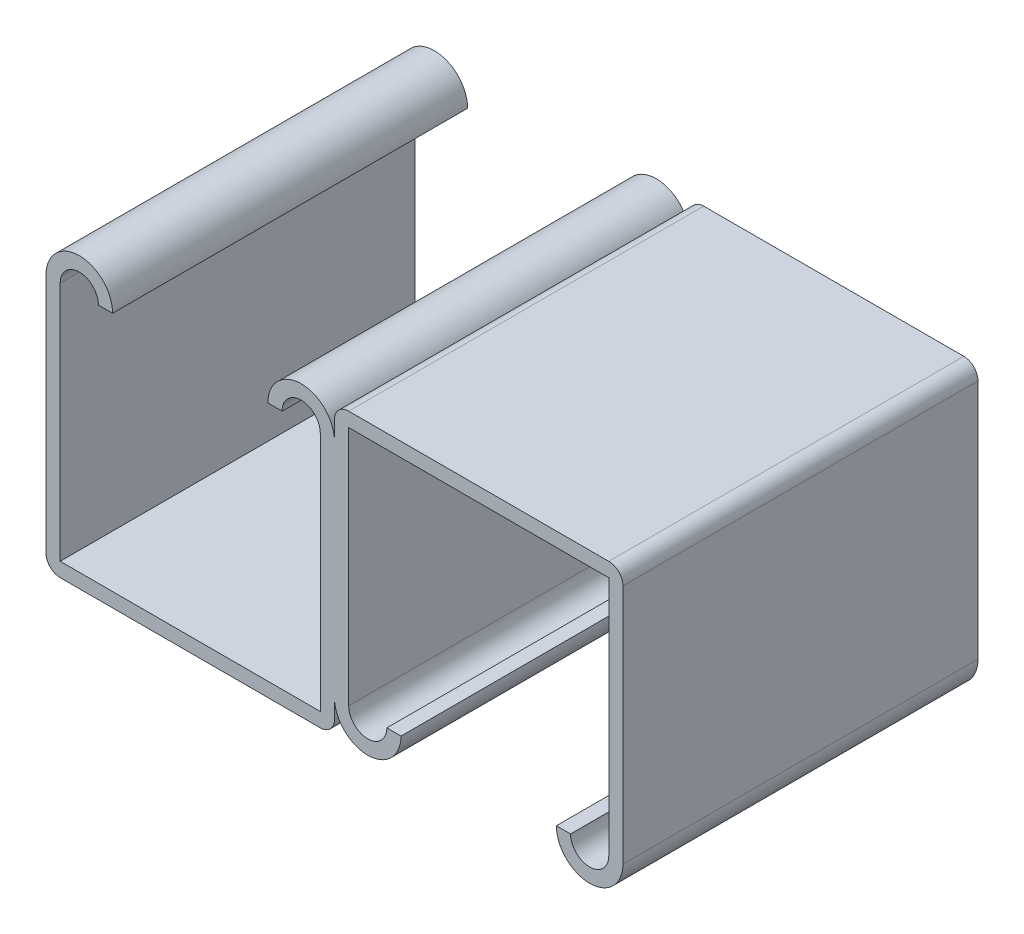
SolidWorks part; units mm, degrees
note: '?' marks a value the reader was unsure of.
ref_plane "Plane1" through (0, 0, 0) normal (0, 0, 1) x (1, 0, 0)
ref_plane "Plane2" through (0, 0, 0) normal (0, 1, 0) x (1, 0, 0)
ref_plane "Plane3" through (0, 0, 0) normal (1, 0, 0) x (0, 0, -1)
sketch "Sketch1" plane through (0, 0, 0) normal (0, 0, 1) x (1, 0, 0)
  line L0 (-20.6375, 7.9375) -> (-20.6375, -9.3027)
  line L1 (-19.6215, -10.3187) -> (-1.016, -10.3187)
  line L2 (0, -9.3027) -> (0, 7.9375)
  line L3 (-16.891, 7.9375) -> (-15.875, 7.9375)
  line L4 (-4.7625, 7.9375) -> (-3.7465, 7.9375)
  line L6 (-19.6215, 7.9375) -> (-19.6215, -9.3027)
  line L7 (-19.6215, -9.3027) -> (-1.016, -9.3027)
  line L8 (-1.016, -9.3027) -> (-1.016, 7.9375)
  line L10 (-44.483, 10.3187) -> (25.4, 10.3187) construction
  arc A0 (0, 7.9375) -> (-4.7625, 7.9375) centre (-2.3813, 7.9375) ccw
  arc A1 (-20.6375, 7.9375) -> (-15.875, 7.9375) centre (-18.2563, 7.9375) cw
  arc A2 (-19.6215, -10.3187) -> (-20.6375, -9.3027) centre (-19.6215, -9.3027) cw
  arc A3 (-1.016, -10.3187) -> (0, -9.3027) centre (-1.016, -9.3027) ccw
  arc A4 (-19.6215, 7.9375) -> (-16.891, 7.9375) centre (-18.2563, 7.9375) cw
  arc A5 (-1.016, 7.9375) -> (-3.7465, 7.9375) centre (-2.3813, 7.9375) ccw
  dimension "D5" = 10.3187
  dimension "D8" = 10.3187
  dimension "D2" = 4.7625
  dimension "D3" = 11.1125
  dimension "D4" = 1.016
  dimension "D6" = 4.7625
extrude "Base-Extrude" add sketch "Sketch1" along normal mid plane 25.4
ref_axis "Axis1" through (0, 0, -50) along (0, 0, 1)?
pattern_circular "CirPattern1" count 2 every 180 about axis through (0, 0, 0) along (0, 0, 1) of "Base-Extrude"
equation "\"D1@Sketch1\" = \"gauge@Sketch1\""
